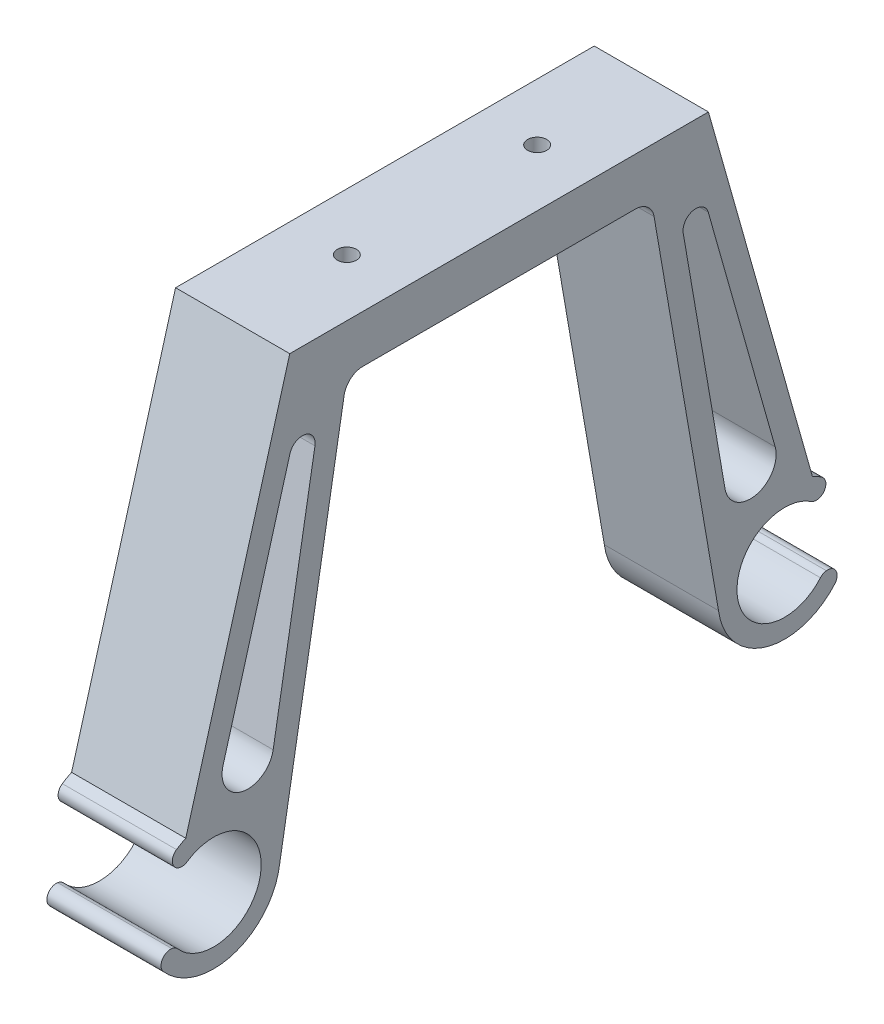
SolidWorks part; units mm, degrees
ref_plane "Front Plane" through (0, 0, 0) normal (0, 0, 1) x (1, 0, 0)
ref_plane "Top Plane" through (0, 0, 0) normal (0, 1, 0) x (1, 0, 0)
ref_plane "Right Plane" through (0, 0, 0) normal (1, 0, 0) x (0, 0, -1)
sketch "Sketch1" plane through (0, 0, 0) normal (1, 0, 0) x (0, 0, -1)
  circle A0 centre (-30, 0) radius 7
  circle A2 centre (-30, 0) radius 5
extrude "Boss-Extrude1" add sketch "Sketch1" along normal blind 12
sketch "Sketch3" plane through (12, 0, 0) normal (1, 0, 0) x (0, 0, -1)
  line L0 (-26, 3) -> (-26.9206, -3.9392)
  line L1 (-26, 3) -> (-39.4553, 4.7851)
  line L2 (-26.9206, -3.9392) -> (-40.3759, -2.1541)
  line L3 (-39.4553, 4.7851) -> (-40.3759, -2.1541)
  line L4 (-37, 0) -> (37, 0) construction
  circle A0 centre (-30, 0) radius 5 construction
  circle A1 centre (-30, 0) radius 7 construction
  point P13 (0, 0)
  dimension "D1" = 7
  dimension "D2" = 3
extrude "Cut-Extrude1" cut sketch "Sketch3" against normal through all
fillet "Fillet1" radius 1 4 edges at (6, 3.9392, 33.0794) (6, 4.2669, 35.5492) (6, -3, 34) (6, -2.6723, 36.4698)
sketch "Sketch4" plane through (12, 0, 0) normal (1, 0, 0) x (0, 0, -1)
  line L0 (-23.0608, -0.9206) -> (-16, 40)
  line L1 (-16, 40) -> (0, 40)
  line L2 (0, 40) -> (0, 45)
  line L3 (0, 45) -> (-22, 45)
  line L4 (-22, 45) -> (-32.9271, 6.3586)
  line L5 (-30, 0) -> (0, 0) construction
  arc A0 (-35.2803, -4.5955) -> (-33.8994, 5.8133) centre (-30, 0) ccw construction
  arc A7 (-33.8994, 5.8133) -> (-33.4739, 3.9915) centre (-33.3423, 4.9828) ccw
  arc A8 (-33.4739, 3.9915) -> (-32.7853, 4.1524) centre (-33.3423, 4.9828) ccw
  arc A9 (-33.7716, -3.2825) -> (-32.7853, 4.1524) centre (-30, 0) ccw
  arc A10 (-33.7716, -3.2825) -> (-34.3945, -2.9477) centre (-34.526, -3.939) ccw
  arc A11 (-34.3945, -2.9477) -> (-35.2803, -4.5955) centre (-34.526, -3.939) ccw
  arc A12 (-35.2803, -4.5955) -> (-33.8994, 5.8133) centre (-30, 0) ccw
  arc A18 (-23.0608, -0.9206) -> (-32.9271, 6.3586) centre (-30, 0) ccw
  dimension "D1" = 16
  dimension "D2" = 22
  dimension "D3" = 5
  dimension "D4" = 40
  dimension "D5" = 6
  dimension "D6" = 0
extrude "Boss-Extrude2" add sketch "Sketch4" against normal up to surface (12 mm away) up to face at (0, 0.1104, 30.8324)
fillet "Fillet2" radius 2 1 edges at (6, 40, 16)
sketch "Sketch6" plane through (12, 0, 0) normal (1, 0, 0) x (0, 0, -1)
  line L0 (-14.9697, 60.6738) -> (-29.6637, 8.7115)
  line L1 (-29.6637, 8.7115) -> (-24.3217, 6.4747)
  line L2 (-24.3217, 6.4747) -> (-14.9697, 60.6738)
  line L3 (-23.0608, -0.9206) -> (-16.2864, 38.3401) construction
  line L4 (-22, 45) -> (-32.9271, 6.3586) construction
  circle A0 centre (-26.4094, 10.2808) radius 2.7045
  circle A1 centre (-20.6801, 35.5189) radius 1.35
  dimension "D1" = 54
  dimension "D3" = 55
  dimension "D5" = 2.7
  dimension "D2" = 2.5
  dimension "D4" = 2.5
extrude "Cut-Extrude2" cut sketch "Sketch6" against normal through all contours A1 L0 A0 L2 | A0 | A1 region at (12, 22.3482, 23.67) region at (12, 10.2808, 26.4094)
mirror "Mirror9" about plane through (-56.5057, 40, 0) normal (0, 0, -1) of bodies 105
sketch "Sketch7" plane through (0, 45, 0) normal (0, 1, 0) x (1, 0, 0)
  line L0 (0, -22) -> (0, 22) construction
  circle A0 centre (6, -10) radius 1
  circle A1 centre (6, 10) radius 1
  point P6 (0, 0)
  dimension "D5" = 2
  dimension "D6" = 2
  dimension "D1" = 6
  dimension "D2" = 6
  dimension "D3" = 10
  dimension "D4" = 10
extrude "Cut-Extrude3" cut sketch "Sketch7" against normal through all
